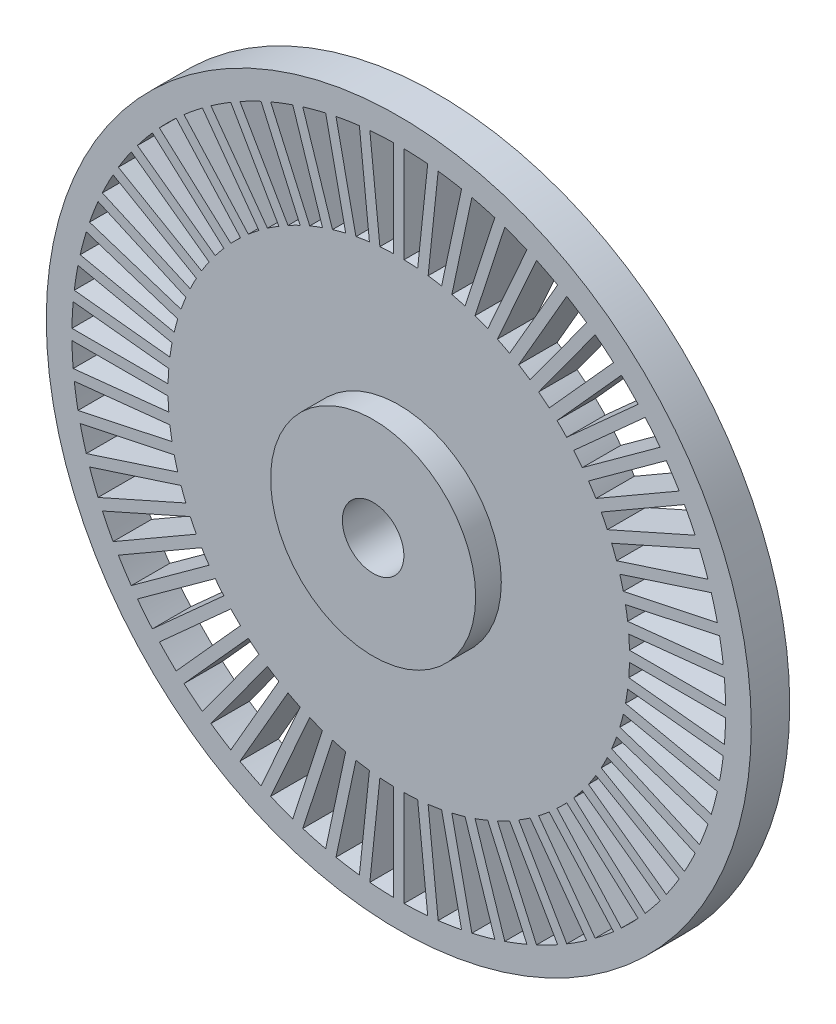
SolidWorks part; units mm, degrees
ref_plane "Płaszczyzna przednia" through (0, 0, 0) normal (0, 0, 1) x (1, 0, 0)
ref_plane "Płaszczyzna górna" through (0, 0, 0) normal (0, 1, 0) x (1, 0, 0)
ref_plane "Płaszczyzna prawa" through (0, 0, 0) normal (1, 0, 0) x (0, 0, -1)
sketch "Szkic1" plane through (0, 0, 0) normal (0, 0, 1) x (1, 0, 0)
  circle A0 centre (0, 0) radius 13.75
  circle A1 centre (0, 0) radius 1.2
  dimension "D1" = 27.5
  dimension "D2" = 2.4
extrude "Dodanie-wyciągnięcie1" add sketch "Szkic1" along normal blind 1.5
sketch "Szkic2" plane through (0, 0, 0) normal (0, 0, -1) x (-1, 0, 0)
  circle A0 centre (0, 0) radius 12.75
  circle A1 centre (0, 0) radius 9
  dimension "D1" = 25.5
  dimension "D2" = 18
extrude "Wytnij-wyciągnięcie1" cut sketch "Szkic2" against normal up to surface (1.5 mm away) up to face at (13.75, 0, 1.5)
sketch "Szkic3" plane through (0, 0, 1.5) normal (0, 0, 1) x (1, 0, 0)
  line L0 (0, 0) -> (0, 12.5303) construction
  line L2 (-0.205, 12.8997) -> (0.205, 12.8997)
  line L3 (-0.205, 12.8997) -> (-0.205, 8.1438)
  line L4 (-0.205, 8.1438) -> (0.205, 8.1438)
  line L5 (0.205, 12.8997) -> (0.205, 8.1438)
  line L6 (-0.205, 12.8997) -> (0.205, 8.1438) construction
  line L7 (-0.205, 8.1438) -> (0.205, 12.8997) construction
  point P3 (0, 10.5217)
  dimension "D1" = 0.41
extrude "Dodanie-wyciągnięcie2" add sketch "Szkic3" against normal up to surface (1.5 mm away) up to face at (1.2, 0, 0)
pattern_circular "Szyk kołowy1" count 60 every 6 about axis through (0, 0, 1.5) along (0, 0, 1) of "Dodanie-wyciągnięcie2"
sketch "Szkic4" plane through (0, 0, 1.5) normal (0, 0, 1) x (1, 0, 0)
  circle A0 centre (0, 0) radius 1.2
  circle A1 centre (0, 0) radius 4
  dimension "D1" = 8
extrude "Dodanie-wyciągnięcie3" add sketch "Szkic4" along normal blind 1
